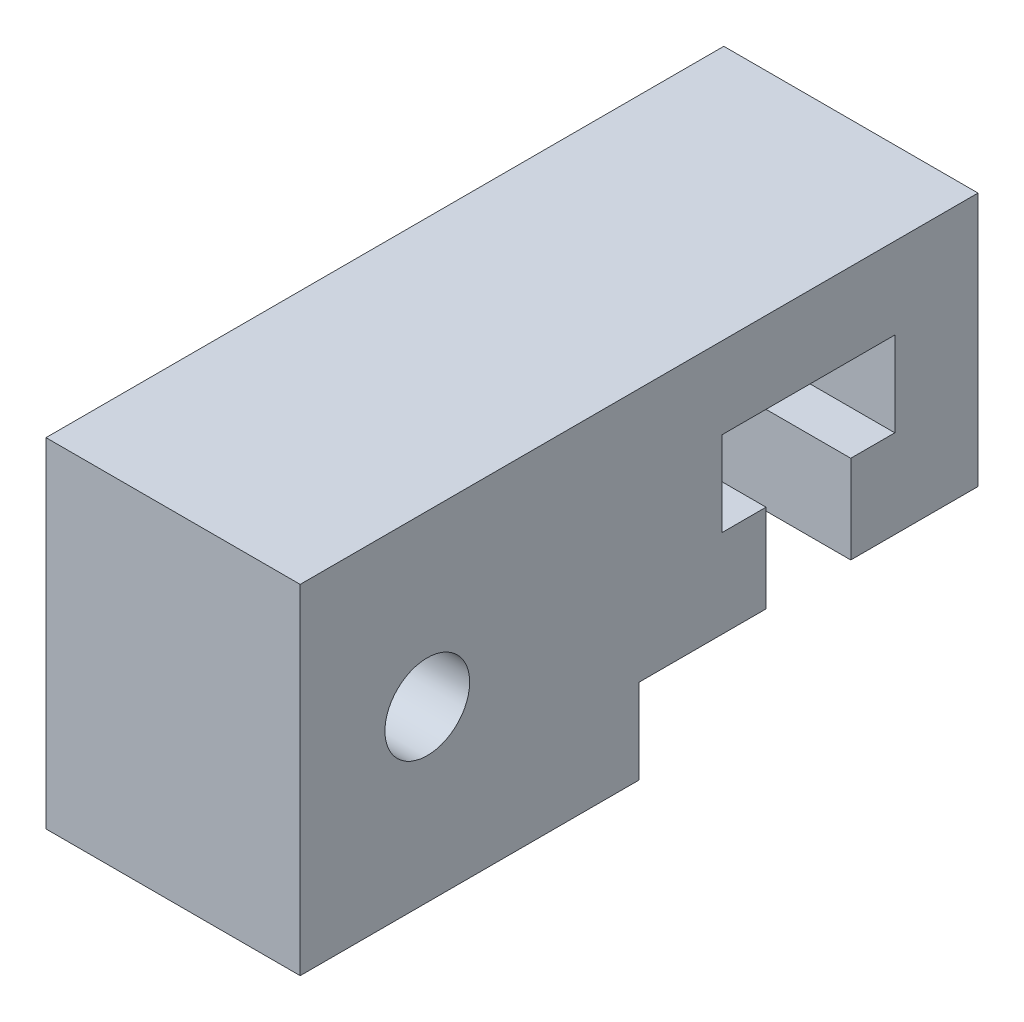
SolidWorks part; units mm, degrees
ref_plane "Front Plane" through (0, 0, 0) normal (0, 0, 1) x (1, 0, 0)
ref_plane "Top Plane" through (0, 0, 0) normal (0, 1, 0) x (1, 0, 0)
ref_plane "Right Plane" through (0, 0, 0) normal (1, 0, 0) x (0, 0, -1)
sketch "Sketch2" plane through (0, 0, 0) normal (1, 0, 0) x (0, 0, -1)
  line L0 (-4.7625, 6.35) -> (-4.7625, -6.35)
  line L1 (-4.7625, -6.35) -> (7.9375, -6.35)
  line L2 (7.9375, -6.35) -> (7.9375, -3.175)
  line L3 (20.6375, -3.175) -> (15.8692, -3.175)
  line L4 (20.6375, -3.175) -> (20.6375, 6.35)
  line L5 (20.6375, 6.35) -> (-4.7625, 6.35)
  line L6 (-19.474, 0) -> (-4.2216, 0) construction
  line L7 (15.8692, -3.175) -> (15.8692, 0.127)
  line L8 (15.8692, 0.127) -> (17.5202, 0.127)
  line L9 (17.5202, 0.127) -> (17.5202, 3.302)
  line L10 (17.5202, 3.302) -> (11.0432, 3.302)
  line L11 (11.0432, 3.302) -> (11.0432, 0.127)
  line L12 (11.0432, 0.127) -> (12.6942, 0.127)
  line L13 (12.6942, 0.127) -> (12.6942, -3.175)
  line L14 (12.6942, -3.175) -> (7.9375, -3.175)
  line L15 (14.2817, 0.9915) -> (14.2817, -22.7495) construction
  circle A0 centre (0, 0) radius 1.5875
  point P10 (-4.7625, 0)
  point P21 (14.2817, 3.302)
  dimension "D2" = 3.175
  dimension "D1" = 12.7
  dimension "D3" = 12.7
  dimension "D4" = 9.525
  dimension "D5" = 4.7625
  dimension "D6" = 25.4
  dimension "D7" = 6.477
  dimension "D8" = 3.175
  dimension "D9" = 6.3558
  dimension "D10" = 6.477
  dimension "D11" = 3.175
  dimension "D12" = 3.175
extrude "Boss-Extrude1" add sketch "Sketch2" along normal blind 4.7625 and the other way blind 4.7625
